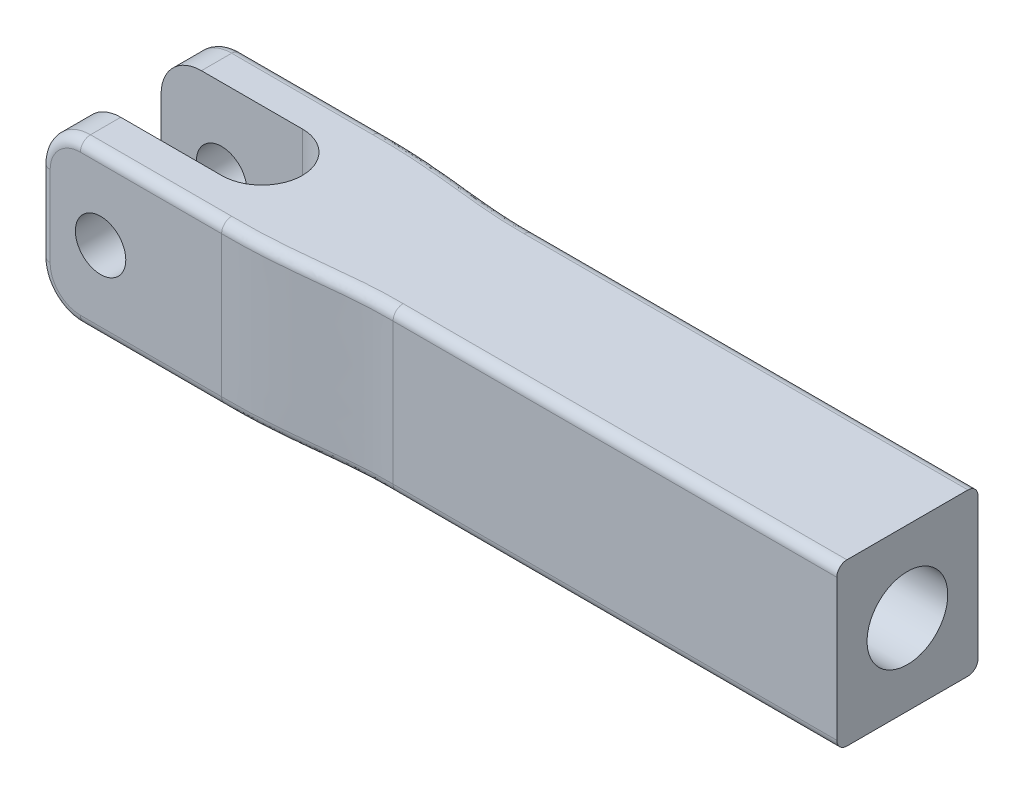
SolidWorks part; units mm, degrees
material "6061-T6 (SS)"
ref_plane "Front Plane" through (0, 0, 0) normal (0, 0, 1) x (1, 0, 0)
ref_plane "Top Plane" through (0, 0, 0) normal (0, 1, 0) x (1, 0, 0)
ref_plane "Right Plane" through (0, 0, 0) normal (1, 0, 0) x (0, 0, -1)
sketch "Sketch1" plane through (0, 0, 0) normal (0, 1, 0) x (1, 0, 0)
  line L0 (0, 0) -> (0, 23.844) construction
  line L1 (0, 0) -> (130.1381, 0) construction
  line L2 (19.05, -6.35) -> (19.05, 6.35)
  line L3 (19.05, 6.35) -> (-9.525, 6.35)
  line L4 (-9.525, 6.35) -> (-9.525, 12.7)
  line L5 (-9.525, 12.7) -> (19.05, 12.7)
  line L6 (28.208, 12.7) -> (16.8042, 12.7) construction
  line L7 (44.45, 11.1125) -> (114.3, 11.1125)
  line L8 (114.3, 11.1125) -> (114.3, -11.1125)
  line L9 (44.45, -11.1125) -> (114.3, -11.1125)
  line L10 (39.043, 11.1125) -> (32.8906, 11.1125) construction
  line L11 (-9.525, -12.7) -> (19.05, -12.7)
  line L12 (-9.525, -6.35) -> (-9.525, -12.7)
  line L13 (19.05, -6.35) -> (-9.525, -6.35)
  spline S0 degree 5 poles (19.05, 12.7) (24.085, 12.7) (29.1201, 12.7) (36.7459, 11.1125) (40.5979, 11.1125) (44.45, 11.1125) knots 0 0 0 0 0 0 1 1 1 1 1 1
  spline S1 degree 5 poles (19.05, -12.7) (24.085, -12.7) (29.1201, -12.7) (36.7459, -11.1125) (40.5979, -11.1125) (44.45, -11.1125) knots 0 0 0 0 0 0 1 1 1 1 1 1
  point P13 (114.3, 0)
  point P18 (19.05, 0)
  dimension "D1" = 12.7
  dimension "D2" = 6.35
  dimension "D3" = 22.225
  dimension "D4" = 9.525
  dimension "D5" = 19.05
  dimension "D6" = 114.3
  dimension "D7" = 25.4
extrude "Boss-Extrude1" add sketch "Sketch1" along normal mid plane 25.4
sketch "Sketch2" plane through (0, 0, 0) normal (0, 0, 1) x (1, 0, 0)
  circle A0 centre (0, 0) radius 3.9688
  dimension "D1" = 7.9375
extrude "Cut-Extrude1" cut sketch "Sketch2" against normal mid plane 127
sketch "Sketch3" plane through (114.3, 0, 0) normal (1, 0, 0) x (0, 0, -1)
  circle A0 centre (0, 0) radius 6.35
  dimension "D1" = 12.7
extrude "Cut-Extrude2" cut sketch "Sketch3" against normal blind 76.2
fillet "Fillet1" radius 6.35 2 edges at (19.05, 0, -6.35) (19.05, 0, 6.35)
fillet "Fillet2" radius 6.35 4 edges at (-9.525, 12.7, 9.525) (-9.525, -12.7, 9.525) (-9.525, -12.7, -9.525) (-9.525, 12.7, -9.525)
fillet "Fillet3" radius 1.5875 18 edges at (79.375, -12.7, -11.1125) (7.9375, -12.7, -12.7) (-7.6651, -10.8401, -12.7) (-9.525, 0, -12.7) (-7.6651, 10.8401, -12.7) (7.9375, 12.7, -12.7) (79.375, -12.7, 11.1125) (7.9375, -12.7, 12.7) (-7.6651, -10.8401, 12.7) (-9.525, 0, 12.7) (-7.6651, 10.8401, 12.7) (7.9375, 12.7, 12.7) (79.375, 12.7, -11.1125) (79.375, 12.7, 11.1125)
